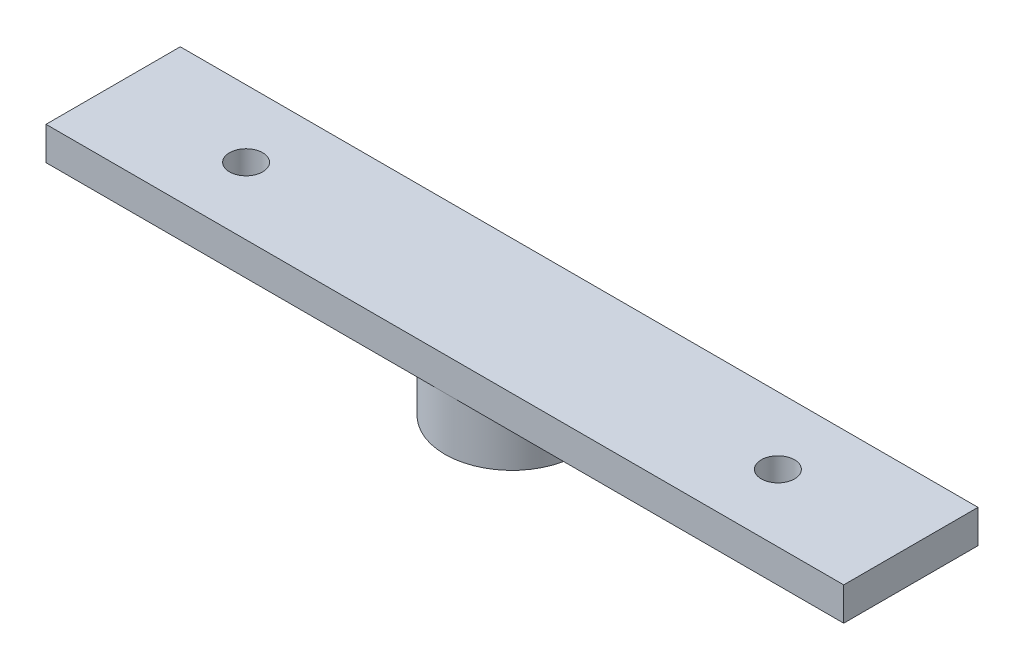
SolidWorks part; units mm, degrees
ref_plane "Front Plane" through (0, 0, 0) normal (0, 0, 1) x (1, 0, 0)
ref_plane "Top Plane" through (0, 0, 0) normal (0, 1, 0) x (1, 0, 0)
ref_plane "Right Plane" through (0, 0, 0) normal (1, 0, 0) x (0, 0, -1)
ref_axis "Axis1" through (0, 97.0223, 0) along (0, -1, 0)
sketch "Sketch1" plane through (0, 0, 0) normal (0, 0, 1) x (1, 0, 0)
  line L0 (3.05, 0) -> (3.05, 4)
  line L7 (5.05, 4) -> (5.05, 0)
  line L8 (5.05, 0) -> (3.05, 0)
  line L9 (3.05, 4) -> (5.05, 4)
  dimension "D1" = 4
  dimension "D2" = 5.05
  dimension "D3" = 3.05
revolve "Revolve1" add sketch "Sketch1" angle 360 about axis through (0, 97.0223, 0) along (0, -1, 0)
sketch "Sketch2" plane through (0, 4, 0) normal (0, 1, 0) x (1, 0, 0)
  line L1 (-30, -5.05) -> (30, -5.05)
  line L2 (-30, -5.05) -> (-30, 5.05)
  line L3 (-30, 5.05) -> (30, 5.05)
  line L4 (30, -5.05) -> (30, 5.05)
  line L5 (-30, -5.05) -> (30, 5.05) construction
  line L6 (-30, 5.05) -> (30, -5.05) construction
  circle A0 centre (0, 0) radius 5.05 construction
  point P0 (0, 0)
  dimension "D1" = 60
extrude "Boss-Extrude1" add sketch "Sketch2" along normal blind 2.5
sketch "Sketch3" plane through (0, 6.5, 0) normal (0, 1, 0) x (1, 0, 0)
  line L0 (-30, 5.05) -> (-30, -5.05) construction
  line L2 (0, -55) -> (0, 55) construction
  circle A6 centre (-20, 0) radius 1.25
  circle A7 centre (20, 0) radius 1.25
  point P2 (0, 0)
  point P9 (-30, 0)
  dimension "D1" = 2.5
  dimension "D2" = 10
extrude "Cut-Extrude1" cut sketch "Sketch3" against normal blind 5
